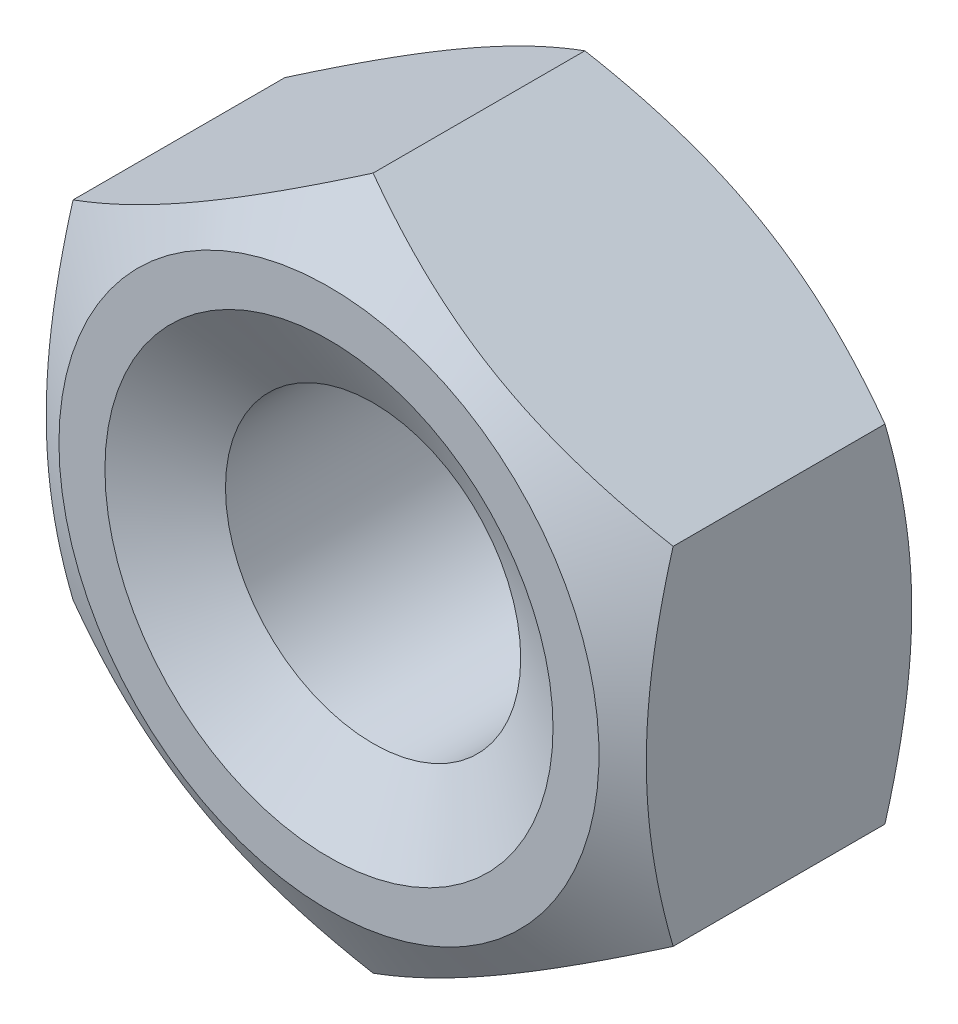
SolidWorks part; units mm, degrees
other "Ссылка на сопряжения"
material "AISI 316 Нержавеющая сталь, лист (SS)"
ref_plane "Плоскость1" through (0, 0, 0) normal (0, 0, 1) x (1, 0, 0)
ref_plane "Плоскость2" through (0, 0, 0) normal (0, 1, 0) x (1, 0, 0)
ref_plane "Плоскость3" through (0, 0, 0) normal (1, 0, 0) x (0, 0, -1)
sketch "Эскиз1" plane through (0, 0, 0) normal (0, 0, 1) x (1, 0, 0)
  line L1 (0, 5.7735) -> (-5, 2.8868)
  line L2 (-5, 2.8868) -> (-5, -2.8868)
  line L3 (-5, -2.8868) -> (0, -5.7735)
  line L4 (0, -5.7735) -> (5, -2.8868)
  line L5 (5, -2.8868) -> (5, 2.8868)
  line L6 (5, 2.8868) -> (0, 5.7735)
  circle A0 centre (0, 0) radius 5 construction
  circle A1 centre (0, 0) radius 2.46
  dimension "rezba" = 4.92
  dimension "S" = 10
extrude "Основание-Вытянуть" add sketch "Эскиз1" along normal blind 5
cosmetic thread "Условное изображение резьбы1" parameters "d"=6
sketch "Эскиз2" plane through (0, 0, 0) normal (1, 0, 0) x (0, 0, -1)
  line L0 (-5, 2.8868) -> (-5, 5.7735) construction
  line L1 (-5, 5.7735) -> (0, 5.7735) construction
  line L2 (-5, 4.5) -> (-5, 5.7735)
  line L3 (-5, 5.7735) -> (-4.2647, 5.7735)
  line L4 (-5, 4.5) -> (-4.2647, 5.7735)
  line L5 (0, 0) -> (-5, 0) construction
  line L6 (-5, 0) -> (0, 0) construction
  line L7 (-5, -2.8868) -> (-5, 2.8868) construction
  line L8 (0, 2.46) -> (-5, 2.46) construction
  line L9 (-4.2647, 2.46) -> (-5, 2.46)
  line L10 (-5, 3.7335) -> (-4.2647, 2.46)
  line L11 (-5, 3.7335) -> (-5, 2.46)
  line L12 (-2.5, 0) -> (-2.5, 3.9594) construction
  line L13 (0, 3.7335) -> (0, 2.46)
  line L14 (0, 3.7335) -> (-0.7353, 2.46)
  line L15 (-0.7353, 2.46) -> (0, 2.46)
  line L16 (0, 4.5) -> (-0.7353, 5.7735)
  line L17 (0, 5.7735) -> (-0.7353, 5.7735)
  line L18 (0, 4.5) -> (0, 5.7735)
  dimension "D1" = 9
  dimension "_" = 30
revolve "Вырез-Повернуть1" cut sketch "Эскиз2" angle 360 about L5
revolve "Скрытый" add sketch "Эскиз2<3>" angle 360 about L5 region at (0, 2.8845, 0.2451)
sketch "Эскиз2<3>" plane through (0, 0, 0) normal (1, 0, 0) x (0, 0, -1) same geometry as "Эскиз2"
